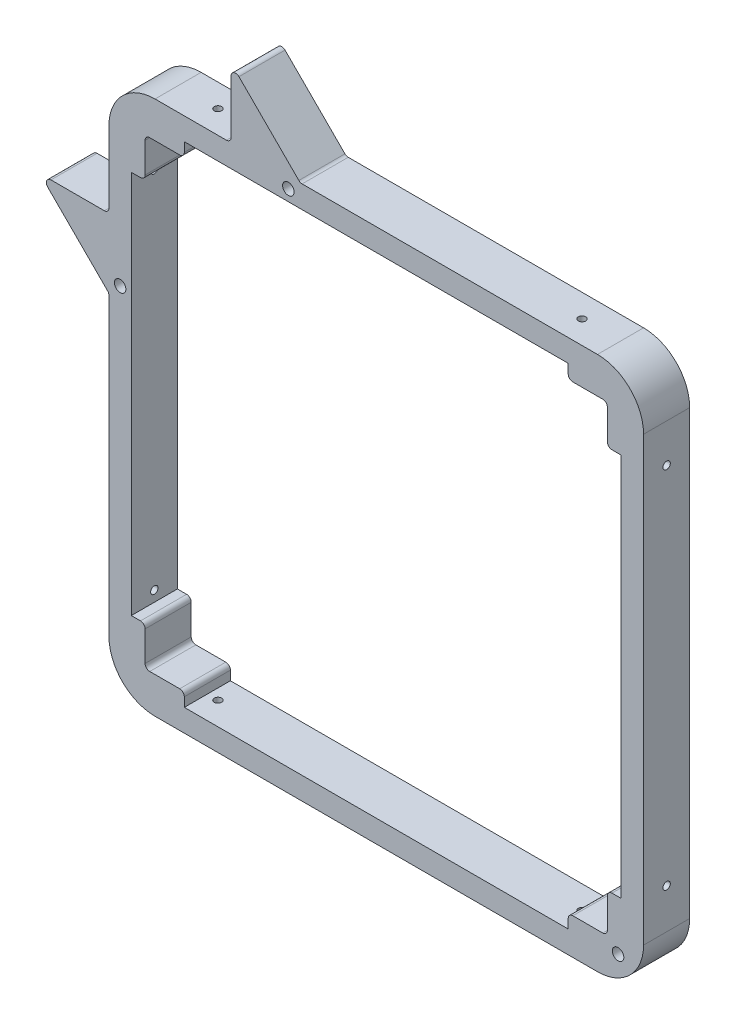
SolidWorks part; units mm, degrees
material "Nylon 101"
ref_plane "Front Plane" through (0, 0, 0) normal (0, 0, 1) x (1, 0, 0)
ref_plane "Top Plane" through (0, 0, 0) normal (0, 1, 0) x (1, 0, 0)
ref_plane "Right Plane" through (0, 0, 0) normal (1, 0, 0) x (0, 0, -1)
sketch "Sketch1" plane through (0, 0, 0) normal (0, 0, 1) x (1, 0, 0)
  line L13 (50.0019, -50.0019) -> (58, -58) construction
  line L14 (53, -41.5) -> (50.0019, -41.5)
  line L17 (41.5, -53) -> (41.5, -50.0019)
  line L18 (50.0019, -44.9586) -> (53, -44.9586)
  line L20 (53, -44.9586) -> (53, -53)
  line L23 (53, -53) -> (44.9586, -53)
  line L24 (44.9586, -53) -> (44.9586, -50.0019)
  line L25 (50.0019, -41.5) -> (50.0019, -50.0019)
  line L27 (50.0019, -50.0019) -> (41.5, -50.0019)
  line L35 (-41.5, 53) -> (41.5, 53)
  line L37 (50.0019, -50.0019) -> (50.0019, -41.5)
  line L38 (41.5, -50.0019) -> (50.0019, -50.0019)
  line L39 (53, -44.9586) -> (50.0019, -44.9586)
  line L40 (53, -53) -> (53, -44.9586)
  line L42 (44.9586, -53) -> (53, -53)
  line L43 (44.9586, -50.0019) -> (44.9586, -53)
  line L44 (53, -41.5) -> (50.0019, -41.5)
  line L45 (41.5, -53) -> (41.5, -50.0019)
  line L47 (53, -41.5) -> (53, 41.5)
  line L50 (41.5, -53) -> (-41.5, -53)
  line L52 (-41.5, -53) -> (-41.5, -50.0019)
  line L53 (-53, -41.5) -> (-50.0019, -41.5)
  line L54 (-44.96, -50.0019) -> (-44.96, -53)
  line L55 (-44.96, -53) -> (-53, -53)
  line L57 (-53, -53) -> (-53, -44.96)
  line L58 (-53, -44.96) -> (-50.0019, -44.96)
  line L59 (-41.5, -50.0019) -> (-50.0019, -50.0019)
  line L60 (-50.0019, -50.0019) -> (-50.0019, -41.5)
  line L61 (-53, -41.5) -> (-53, 41.5)
  line L63 (58, 58) -> (58, -58)
  line L65 (-50.0019, -50.0019) -> (-41.5, -50.0019)
  line L66 (-50.0019, -41.5) -> (-50.0019, -50.0019)
  line L67 (-44.96, -53) -> (-44.96, -50.0019)
  line L68 (-53, -53) -> (-44.96, -53)
  line L70 (-53, -44.96) -> (-53, -53)
  line L71 (-50.0019, -44.96) -> (-53, -44.96)
  line L72 (-41.5, -53) -> (-41.5, -50.0019)
  line L73 (-53, -41.5) -> (-50.0019, -41.5)
  line L75 (58, -58) -> (-58, -58)
  line L77 (-50.0019, -50.0019) -> (-58, -58) construction
  line L79 (-58, -58) -> (-58, 58)
  line L81 (-53, 41.5) -> (-50.0019, 41.5)
  line L82 (-41.5, 53) -> (-41.5, 50.0019)
  line L83 (-50.0019, 44.96) -> (-53, 44.96)
  line L84 (-53, 44.96) -> (-53, 53)
  line L86 (-53, 53) -> (-44.96, 53)
  line L87 (-44.96, 53) -> (-44.96, 50.0019)
  line L88 (-50.0019, 41.5) -> (-50.0019, 50.0019)
  line L89 (-50.0019, 50.0019) -> (-41.5, 50.0019)
  line L90 (-58, 58) -> (58, 58)
  line L94 (-50.0019, 50.0019) -> (-50.0019, 41.5)
  line L95 (-41.5, 50.0019) -> (-50.0019, 50.0019)
  line L96 (-53, 44.96) -> (-50.0019, 44.96)
  line L97 (-53, 53) -> (-53, 44.96)
  line L99 (-44.96, 53) -> (-53, 53)
  line L100 (-44.96, 50.0019) -> (-44.96, 53)
  line L101 (-53, 41.5) -> (-50.0019, 41.5)
  line L102 (-41.5, 53) -> (-41.5, 50.0019)
  line L106 (-50.0019, 50.0019) -> (-58, 58) construction
  line L110 (41.5, 53) -> (41.5, 50.0019)
  line L111 (53, 41.5) -> (50.0019, 41.5)
  line L112 (44.9586, 50.0019) -> (44.9586, 53)
  line L113 (44.9586, 53) -> (53, 53)
  line L115 (53, 53) -> (53, 44.96)
  line L116 (53, 44.96) -> (50.0019, 44.96)
  line L117 (41.5, 50.0019) -> (50.0019, 50.0019)
  line L118 (50.0019, 50.0019) -> (50.0019, 41.5)
  line L123 (50.0019, 50.0019) -> (41.5, 50.0019)
  line L124 (50.0019, 41.5) -> (50.0019, 50.0019)
  line L125 (44.9586, 53) -> (44.9586, 50.0019)
  line L126 (53, 53) -> (44.9586, 53)
  line L128 (53, 44.96) -> (53, 53)
  line L129 (50.0019, 44.96) -> (53, 44.96)
  line L130 (41.5, 53) -> (41.5, 50.0019)
  line L131 (53, 41.5) -> (50.0019, 41.5)
  line L135 (50.0019, 50.0019) -> (58, 58) construction
  point P2 (0, 58)
  point P4 (0, 53)
  point P6 (0, -53)
  point P7 (0, -58)
  point P10 (53, 0)
  point P11 (-53, 0)
  point P16 (-58, 0)
  point P17 (58, 0)
  dimension "D1" = 106
  dimension "D2" = 5
  dimension "D3" = 2.9981
extrude "base" add sketch "Sketch1" along normal mid plane 10 contours L20 L13 L14 L25 L18 | L13 L23 L24 L27 L17 | L13 L27 L24 L23 | L25 L13 L20 L18 | L117 L118 L116 L115 L113 L112 | L88 L89 L87 L86 L84 L83 | L59 L60 L58 L57 L55 L54 region at (51.5009, -45.0723, 0) region at (50.1156, 47.4809, 0) region at (-45.0737, -51.5009, 0) region at (-47.4809, 50.1156, 0) region at (56.3595, 0, 0)
ref_plane "Plane3" through (0, 0, 15) normal (0, 0, 1) x (1, 0, 0)
sketch "Sketch7" plane through (0, 0, 15) normal (0, 0, 1) x (1, 0, 0)
  line L0 (-41.65, 53.15) -> (41.65, 53.15)
  line L1 (41.65, 53.15) -> (41.65, 50.1519)
  line L2 (41.65, 50.1519) -> (50.1519, 50.1519)
  line L3 (50.1519, 50.1519) -> (50.1519, 41.65)
  line L4 (50.1519, 41.65) -> (53.15, 41.65)
  line L5 (53.15, 41.65) -> (53.15, -41.65)
  line L6 (53.15, -41.65) -> (50.1519, -41.65)
  line L7 (50.1519, -41.65) -> (50.1519, -50.1519)
  line L8 (50.1519, -50.1519) -> (41.65, -50.1519)
  line L9 (41.65, -50.1519) -> (41.65, -53.15)
  line L10 (41.65, -53.15) -> (-41.65, -53.15)
  line L11 (-41.65, -53.15) -> (-41.65, -50.1519)
  line L12 (-41.65, -50.1519) -> (-50.1519, -50.1519)
  line L13 (-50.1519, -50.1519) -> (-50.1519, -41.65)
  line L14 (-50.1519, -41.65) -> (-53.15, -41.65)
  line L15 (-53.15, -41.65) -> (-53.15, 41.65)
  line L16 (-53.15, 41.65) -> (-50.1519, 41.65)
  line L17 (-50.1519, 41.65) -> (-50.1519, 50.1519)
  line L18 (-50.1519, 50.1519) -> (-41.65, 50.1519)
  line L19 (-41.65, 50.1519) -> (-41.65, 53.15)
  line L21 (-41.5, 53) -> (41.5, 53) construction
  line L22 (-41.5, 53) -> (-41.5, 50.0019) construction
  line L23 (-50.0019, 50.0019) -> (-41.5, 50.0019) construction
  line L24 (-50.0019, 41.5) -> (-50.0019, 50.0019) construction
  line L25 (-53, 41.5) -> (-50.0019, 41.5) construction
  line L26 (-53, -41.5) -> (-53, 41.5) construction
  line L27 (-53, -41.5) -> (-50.0019, -41.5) construction
  line L28 (-50.0019, -50.0019) -> (-50.0019, -41.5) construction
  line L29 (-41.5, -50.0019) -> (-50.0019, -50.0019) construction
  line L30 (-41.5, -53) -> (-41.5, -50.0019) construction
  line L31 (41.5, -53) -> (-41.5, -53) construction
  line L32 (41.5, -53) -> (41.5, -50.0019) construction
  line L33 (50.0019, -41.5) -> (50.0019, -50.0019) construction
  line L34 (53, -41.5) -> (53, 41.5) construction
  line L35 (50.0019, 50.0019) -> (50.0019, 41.5) construction
  line L36 (53, 41.5) -> (50.0019, 41.5) construction
  line L37 (41.5, 50.0019) -> (50.0019, 50.0019) construction
  dimension "D1" = 0.15
  dimension "D2" = 0.15
  dimension "D3" = 0.15
  dimension "D4" = 0.15
  dimension "D5" = 0.15
  dimension "D6" = 0.15
  dimension "D7" = 0.15
  dimension "D8" = 0.15
  dimension "D9" = 0.15
  dimension "D10" = 0.15
  dimension "D11" = 0.15
  dimension "D12" = 0.15
  dimension "D13" = 0.15
  dimension "D14" = 0.15
  dimension "D15" = 0.15
  dimension "D16" = 0.15
  dimension "D17" = 0.15
ref_plane "arm plane" through (0, 0, 0) normal (0.7071, 0.7071, 0) x (0.7071, -0.7071, 0)
sketch "Sketch2" plane through (0, 0, 0) normal (0.7071, 0.7071, 0) x (0.7071, -0.7071, 0)
  line L4 (70.9255, 5) -> (82.0244, 5)
  line L6 (66.8216, 5) -> (8.1317, 5) construction
  line L8 (82.0244, 5) -> (82.0244, 23.31)
  line L9 (82.0244, 23.31) -> (5.0244, 23.31)
  line L12 (5.0244, 23.31) -> (16.3344, 12)
  line L13 (16.3344, 12) -> (70.9255, 12)
  line L14 (70.9255, 12) -> (70.9255, 5)
  dimension "D1" = 45
  dimension "D2" = 11.31
  dimension "D3" = 77
  dimension "D4" = 7
extrude "arm" add sketch "Sketch2" along normal mid plane 10
sketch "Sketch3" plane through (0, 0, 0) normal (0, 0, 1) x (1, 0, 0)
  line L1 (61.5355, -54.4645) -> (54.4645, -61.5355) construction
  line L6 (58, 58) -> (58, -50.9289) construction
  line L7 (50.9289, -58) -> (-58, -58) construction
  line L8 (8.0146, -15.0857) -> (46.6163, -53.6874) construction
  line L9 (58, -50.9289) -> (61.5355, -54.4645) construction
  line L10 (54.818, -61.8891) -> (61.8891, -54.818)
  line L11 (61.8891, -54.818) -> (58, -50.9289)
  line L12 (58, -50.9289) -> (58, -58)
  line L13 (58, -58) -> (50.9289, -58)
  line L14 (50.9289, -58) -> (54.818, -61.8891)
  dimension "D1" = 0.5
extrude "Cut-Extrude1" cut sketch "Sketch3" against normal through all
ref_plane "Plane2" through (0, 0, -5) normal (0, 0, -1) x (-1, 0, 0)
sketch "Sketch5" plane through (0, 0, -5) normal (0, 0, -1) x (-1, 0, 0)
  line L0 (-46.6163, -53.6874) -> (-43.0808, -50.1519)
  line L7 (-50.1519, -43.0808) -> (-53.6874, -46.6163)
  line L8 (-53.6874, -46.6163) -> (-53.6874, -53.6874)
  line L9 (-50.0019, -50.0019) -> (-58, -58) construction
  line L10 (-53.6874, -53.6874) -> (-46.6163, -53.6874)
  line L12 (-53.6874, -46.6163) -> (-58, -50.9289) construction
  line L14 (-50.1519, -41.65) -> (-50.1519, -50.1519) construction
  line L15 (-50.1519, -50.1519) -> (-41.65, -50.1519) construction
  line L16 (-50.1519, -43.0808) -> (-50.1519, -50.1519)
  line L17 (-50.1519, -50.1519) -> (-43.0808, -50.1519)
  dimension "D1" = 5
  dimension "D2" = 10
extrude "Boss-Extrude4" add sketch "Sketch5" along normal up to surface (7 mm away) contours L8 L10 L0 L7 | L7 L8 L10 L0 L17 L16 region at (50.1519, -53.5374, -5) up to face at (30.851, -30.851, -12)
ref_plane "Mirror Plane" through (10.0177, -10.0177, -14.1672) normal (-0.5, 0.5, 0.7071) x (0.866, 0.2887, 0.4082)
sketch "Sketch9" plane through (10.0177, -10.0177, -14.1672) normal (-0.5, 0.5, 0.7071) x (0.866, 0.2887, 0.4082)
  line L0 (-9.2532, -10.2967) -> (12.7922, 5.2918)
  line L1 (-30.6152, 19.9137) -> (12.7922, 5.2918) construction
  line L2 (5.852, 0.3843) -> (-2.313, -5.3892) construction
  line L3 (-9.2532, -10.2967) -> (-30.6152, 19.9137)
  line L4 (-30.6152, 19.9137) -> (-8.5698, 35.5021)
  line L5 (-8.5698, 35.5021) -> (12.7922, 5.2918)
  line L6 (-8.5698, 35.5021) -> (-9.2532, -10.2967) construction
  line L7 (-8.8089, 34.1083) -> (-29.2213, 19.6745)
  line L8 (-29.2213, 19.6745) -> (-9.0141, -8.9028)
  line L9 (-9.0141, -8.9028) -> (11.3984, 5.5309)
  line L10 (11.3984, 5.5309) -> (-8.8089, 34.1083)
  line L11 (-9.0141, -8.9028) -> (-8.8089, 34.1083) construction
  line L12 (-29.2213, 19.6745) -> (11.3984, 5.5309) construction
  point P4 (1.7695, -2.5025)
  point P5 (1.7695, -2.5025)
  point P12 (-8.9115, 12.6027)
  point P13 (-8.9115, 12.6027)
  dimension "D1" = 27
  dimension "D2" = 37
  dimension "D3" = 1
  dimension "D4" = 1
extrude "Boss-Extrude5" add sketch "Sketch9" along normal blind 4
extrude "Boss-Extrude6" add sketch "Sketch9<2>" along normal blind 1 contours L9 L10 L7 L8 region at (2.3002, -2.3002, -25.0815)
sketch "Sketch9<2>" plane through (10.0177, -10.0177, -14.1672) normal (-0.5, 0.5, 0.7071) x (0.866, 0.2887, 0.4082) same geometry as "Sketch9"
extrude "clearance" cut sketch "Sketch7" against normal up to surface (20 mm away) up to face at (0, 0, -5)
sketch "Sketch10" plane through (0, 0, 0) normal (0, 1, 0) x (1, 0, 0)
  line L0 (41.65, 5) -> (41.65, -5) construction
  circle A0 centre (39.65, 0) radius 0.8
  circle A1 centre (-39.35, 0) radius 0.8
  point P5 (41.65, 0)
  dimension "D1" = 1.6
  dimension "D2" = 2
  dimension "D3" = 79
hole_wizard "M2x0.4 Tapped Hole1" positions "Sketch11" profile "Sketch12" tap size "M2x0.4" standard "ANSI Metric" end condition through all
sketch "Sketch11" plane through (0, 0, 0) normal (0, 1, 0) x (1, 0, 0)
  point P0 (-39.35, 0)
  point P2 (39.65, 0)
sketch "Sketch12" plane through (-39.35, 0, 0) normal (1, 0, 0) x (0, 0, -1)
  line L0 (0, 0) -> (0, 58)
  line L1 (0, 58) -> (0.8, 58)
  line L2 (0.8, 58) -> (0.8, 0)
  line L5 (0.8, 0) -> (0, 0)
  line L11 (0, -6.35) -> (0, 107.95) construction
  dimension "Thru Tap Drill Dia." = 1.6
  dimension "Thru Tap Drill Depth" = 58
cosmetic thread "Hole Thread1" parameters "D2"=2
cosmetic thread "Hole Thread2" parameters "D2"=2
mirror "Mirror1" about plane through (0, 0, 0) normal (0, 1, 0) of "M2x0.4 Tapped Hole1"
cosmetic thread "Hole Thread3" parameters "D2"=2
cosmetic thread "Hole Thread4" parameters "D2"=2
sketch "Sketch13" plane through (0, 0, 0) normal (1, 0, 0) x (0, 0, -1)
  line L2 (5, 41.65) -> (-5, 41.65) construction
  circle A0 centre (0, 39.65) radius 0.8
  circle A1 centre (0, -39.35) radius 0.8
  dimension "D1" = 1.6
  dimension "D3" = 79
  dimension "D2" = 2
hole_wizard "M2x0.4 Tapped Hole2" positions "Sketch14" profile "Sketch15" tap size "M2x0.4" standard "ANSI Metric" end condition through all
sketch "Sketch14" plane through (0, 0, 0) normal (1, 0, 0) x (0, 0, -1)
  point P0 (0, 39.65)
  point P3 (0, -39.35)
sketch "Sketch15" plane through (0, 39.65, 0) normal (0, 1, 0) x (0, 0, 1)
  line L0 (0, 0) -> (0, 58)
  line L1 (0, 58) -> (0.8, 58)
  line L2 (0.8, 58) -> (0.8, 0)
  line L5 (0.8, 0) -> (0, 0)
  line L11 (0, -6.35) -> (0, 107.95) construction
  dimension "Thru Tap Drill Dia." = 1.6
  dimension "Thru Tap Drill Depth" = 58
cosmetic thread "Hole Thread5" parameters "D2"=2
cosmetic thread "Hole Thread6" parameters "D2"=2
mirror "Mirror2" about plane through (0, 0, 0) normal (1, 0, 0) of "M2x0.4 Tapped Hole2"
cosmetic thread "Hole Thread7" parameters "D2"=2
cosmetic thread "Hole Thread8" parameters "D2"=2
sketch "Sketch16" plane through (0, 0, -5) normal (0, 0, -1) x (-1, 0, 0)
  line L5 (53.15, 21.65) -> (109.7185, 78.2185)
  line L6 (53.15, -41.65) -> (53.15, 41.65) construction
  line L8 (109.7185, 78.2185) -> (109.7185, 68.2185)
  line L10 (-58, -58) -> (58, 58) construction
  line L18 (109.7185, 68.2185) -> (53.15, 11.65)
  line L19 (53.15, 11.65) -> (53.15, 21.65)
  dimension "D1" = 80
  dimension "D2" = 10
  dimension "D3" = 20
extrude "extender" add sketch "Sketch16" along normal blind 18.31 contours L19 L18 L8 L5 region at (-81.4343, 44.9343, -5)
ref_plane "Plane5" through (-15.75, -15.75, 0) normal (0.7071, 0.7071, 0) x (0.7071, -0.7071, 0)
sketch "Sketch17" plane through (-15.75, -15.75, 0) normal (0.7071, 0.7071, 0) x (0.7071, -0.7071, 0)
  line L0 (-132.8916, 23.31) -> (-132.8916, 5)
  line L1 (-121.5816, 12) -> (-110.2716, 23.31)
  line L3 (-110.2716, 23.31) -> (-132.8916, 23.31)
  line L5 (-59.7505, 5) -> (-132.8916, 5) construction
  line L6 (-52.8916, 23.31) -> (-132.8916, 23.31) construction
  line L7 (-121.5816, 12) -> (-121.5816, 5)
  line L8 (-121.5816, 5) -> (-132.8916, 5)
  dimension "D1" = 45
  dimension "D2" = 7
  dimension "D3" = 11.31
extrude "angled horizontal" add sketch "Sketch17" along normal up to vertex (30.4056 mm away) up to point (-41.65, 53.15, -5)
sketch "Sketch21" plane through (0, 0, 0) normal (0, 0, 1) x (1, 0, 0)
  line L0 (-58, 16.5) -> (-58, 31.5)
  line L1 (-73, 31.5) -> (-58, 31.5)
  line L2 (-73, 31.5) -> (-58, 16.5)
  line L6 (-109.7185, 68.2185) -> (-58, 16.5) construction
  line L7 (-58, -58) -> (-58, 58) construction
  line L8 (3.8891, -3.8891) -> (-3.8891, 3.8891) construction
  line L9 (-31.5, 73) -> (-16.5, 58)
  line L10 (-31.5, 73) -> (-31.5, 58)
  line L11 (-16.5, 58) -> (-31.5, 58)
  dimension "D2" = 15
extrude "Arm Holder" add sketch "Sketch21" along normal up to surface (5 mm away) and the other way up to surface (5 mm away) up to face at (0, 0, 5) other way up to face at (-86.514, 64.4426, -5)
ref_plane "Plane7" through (-47.2282, 47.2282, -66.7908) normal (0.5, -0.5, 0.7071) x (0.866, 0.2887, -0.4082)
sketch "Sketch19" plane through (-47.2282, 47.2282, -66.7908) normal (0.5, -0.5, 0.7071) x (0.866, 0.2887, -0.4082)
  line L0 (-55.7578, 55.4737) -> (-34.3958, 25.2634)
  line L1 (-38.097, 67.9618) -> (-62.923, 50.4071) construction
  line L2 (-38.097, 67.9618) -> (-28.8624, 54.9022) construction
  line L5 (-55.7578, 55.4737) -> (-33.7124, 71.0622)
  line L6 (-33.7124, 71.0622) -> (-12.3504, 40.8518)
  line L7 (-12.3504, 40.8518) -> (-34.3958, 25.2634)
  line L8 (-55.7578, 55.4737) -> (-12.3504, 40.8518) construction
  line L9 (-33.7124, 71.0622) -> (-34.3958, 25.2634) construction
  line L10 (-54.3639, 55.2346) -> (-33.9515, 69.6683)
  line L11 (-33.9515, 69.6683) -> (-13.7443, 41.091)
  line L12 (-13.7443, 41.091) -> (-34.1567, 26.6572)
  line L13 (-34.1567, 26.6572) -> (-54.3639, 55.2346)
  line L14 (-54.3639, 55.2346) -> (-13.7443, 41.091) construction
  line L15 (-33.9515, 69.6683) -> (-34.1567, 26.6572) construction
  dimension "D1" = 21.63
  dimension "D2" = 37
  dimension "D3" = 27
  dimension "D4" = 1
  dimension "D5" = 1
  dimension "D6" = 1
  dimension "D7" = 1
extrude "Boss-Extrude9" add sketch "Sketch19" along normal blind 4
extrude "Boss-Extrude10" add sketch "Sketch19<2>" along normal blind 1 contours L13 L12 L11 L10 region at (-76.7199, 76.7224, -25.0815)
sketch "Sketch19<2>" plane through (-47.2282, 47.2282, -66.7908) normal (0.5, -0.5, 0.7071) x (0.866, 0.2887, -0.4082) same geometry as "Sketch19"
fillet "Fillet1" radius 1 12 edges at (50.1519, -41.65, 0) (41.65, -50.1519, 0) (-50.1519, -41.65, 0) (-41.65, -50.1519, 0) (-50.1519, 41.65, 0) (-41.65, 50.1519, 0) (41.65, 50.1519, 0) (50.1519, 41.65, 0) (50.1519, 50.1519, 0) (50.1519, -50.1519, -3.5) (-50.1519, -50.1519, 0) (-50.1519, 50.1519, 0)
fillet "Fillet2" radius 10 4 edges at (58, -58, -9.155) (58, 58, 0) (-58, 58, 0) (-58, -58, 0)
mirror "U part of Outside arm" about plane through (0, 0, 0) normal (0.7071, 0.7071, 0) of "angled horizontal", "extender"
hole_wizard "M3x0.5 Tapped Hole1" positions "Sketch26" profile "Sketch27" tap size "M3x0.5" standard "ANSI Metric" end condition through all
sketch "Sketch26" plane through (0, 0, -23.31) normal (0, 0, -1) x (-1, 0, 0)
  line L0 (53.15, 11.65) -> (53.15, 21.65) construction
  line L1 (53.15, 21.65) -> (93.7238, 62.2238) construction
  point P0 (55.575, 19.0758)
  dimension "D1" = 2.425
  dimension "D2" = 3.535
sketch "Sketch27" plane through (-55.575, 19.0758, -23.31) normal (1, 0, 0) x (0, 1, 0)
  line L0 (0, 0) -> (0, 28.31)
  line L1 (0, 28.31) -> (1.25, 28.31)
  line L2 (1.25, 28.31) -> (1.25, 0)
  line L5 (1.25, 0) -> (0, 0)
  line L11 (0, -6.35) -> (0, 107.95) construction
  dimension "Thru Tap Drill Dia." = 2.5
  dimension "Thru Tap Drill Depth" = 28.31
cosmetic thread "Hole Thread10" parameters "D2"=3
hole_wizard "M3x0.5 Tapped Hole2" positions "Sketch28" profile "Sketch29" tap size "M3x0.5" standard "ANSI Metric" end condition through all
sketch "Sketch28" plane through (0, 0, -23.31) normal (0, 0, -1) x (-1, 0, 0)
  line L1 (-57.6593, -50.5882) -> (-7.0883, -0.0172) construction
  arc A0 (-57.6593, -50.5882) -> (-50.5882, -57.6593) centre (-48, -48) ccw construction
  point P0 (-52.4654, -52.4654)
  point P11 (-55.0711, -55.0711)
  dimension "D1" = 5
  dimension "D2" = 3.685
sketch "Sketch29" plane through (52.4654, -52.4654, -23.31) normal (1, 0, 0) x (0, 1, 0)
  line L0 (0, 0) -> (0, 28.31)
  line L1 (0, 28.31) -> (1.25, 28.31)
  line L2 (1.25, 28.31) -> (1.25, 0)
  line L5 (1.25, 0) -> (0, 0)
  line L11 (0, -6.35) -> (0, 107.95) construction
  dimension "Thru Tap Drill Dia." = 2.5
  dimension "Thru Tap Drill Depth" = 28.31
cosmetic thread "Hole Thread13" parameters "D2"=3
mirror "Mirror3" about plane through (0, 0, 0) normal (0.7071, 0.7071, 0) of "M3x0.5 Tapped Hole1"
cosmetic thread "Hole Thread12" parameters "D2"=3
split "Split1" bodies to split 132 130 resulting bodies 128 split by face at (43.3091, 18.4055, -5)
fillet "Fillet3" radius 1 6 edges at (-58, 31.5, 0) (-58, 16.5, 0) (-31.5, 58, 0) (-16.5, 58, 0) (-31.5, 73, 0) (-73, 31.5, 0)
